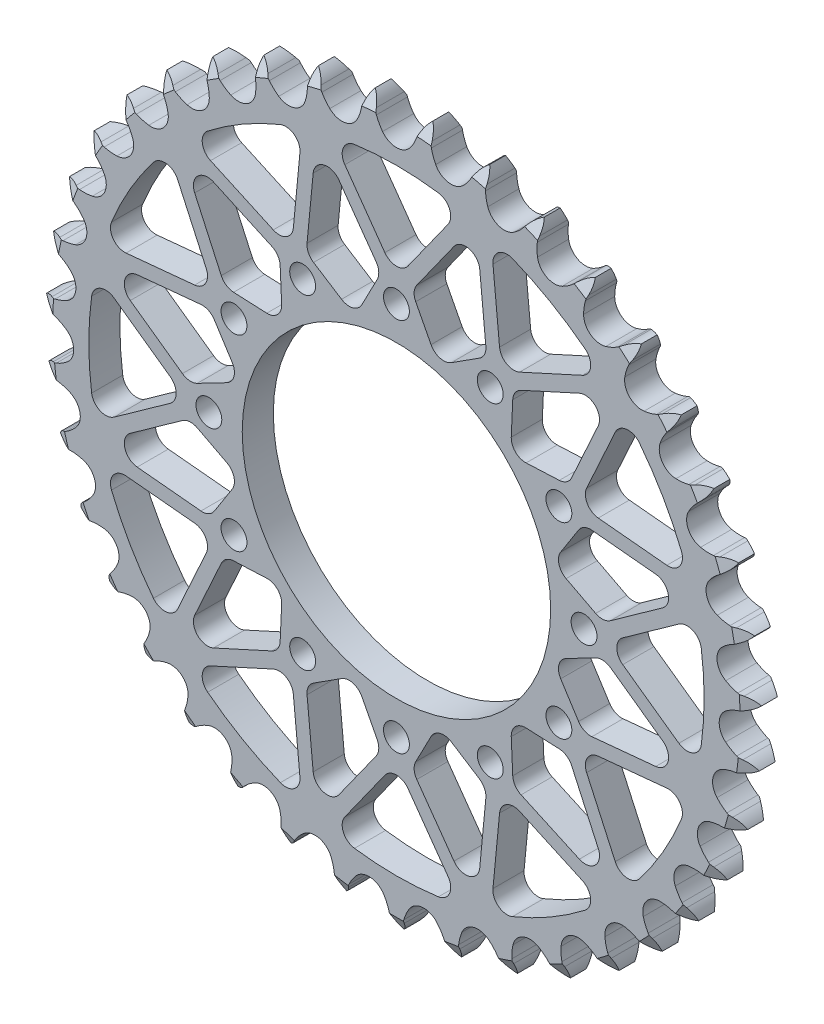
SolidWorks part; units mm, degrees
note: '?' marks a value the reader was unsure of.
material "7075-T6 (SN)"
ref_plane "Front Plane" through (0, 0, 0) normal (0, 0, 1) x (1, 0, 0)
ref_plane "Top Plane" through (0, 0, 0) normal (0, 1, 0) x (1, 0, 0)
ref_plane "Right Plane" through (0, 0, 0) normal (1, 0, 0) x (0, 0, -1)
sketch "Work Sketch" plane through (0, 0, 0) normal (0, 0, 1) x (1, 0, 0)
  line L0 (0, 0) -> (0, 160.4542) construction
  line L1 (-112.0919, 78.9148) -> (87.2579, 78.9148) construction
  line L2 (5.102, 120.8822) -> (5.102, 112.9699) construction
  line L3 (-12.8497, 82.6953) -> (16.7256, 82.6953) construction
  line L4 (5.102, 82.6953) -> (-6.0879, 74.4036) construction
  line L5 (5.102, 82.6953) -> (-4.6505, 79.1506) construction
  line L6 (-4.6505, 79.1506) -> (-6.8863, 85.3019)
  line L7 (-11.5114, 78.0206) -> (-7.1525, 78.0206) construction
  line L8 (-11.0765, 124.7602) -> (-11.0765, 110.2345) construction
  line L9 (0, 0) -> (-3.4402, 42.6146) construction
  circle A0 centre (0, 0) radius 78.9148
  circle A1 centre (0, 78.9148) radius 4.0088
  arc A2 (-4.6505, 79.1506) -> (-3.2209, 76.5281) centre (5.0804, 82.7541) ccw
  circle A3 centre (-11.0765, 78.0206) radius 6.4254
  point P23 (-3.2209, 76.5281)
  dimension "D1" = 157.8295
  dimension "D8" = 10.3767
  dimension "D2" = 8.0177
  dimension "D3" = 5.102
  dimension "D4" = 3.7806
  dimension "D5" = 36.538
  dimension "D6" = 16.564
  dimension "D7" = 10.3767
  dimension "D9" = 0.8942
  dimension "D10" = 11.0765
  dimension "D11" = 4.615
sketch "Teeth Sketch" plane through (0, 0, 0) normal (0, 0, 1) x (1, 0, 0)
  line L0 (5.0376, 80.2155) -> (4.6505, 79.1506)
  line L1 (-7.4865, 92.7372) -> (-4.7839, 59.2593) construction
  line L2 (0, 0) -> (-10.9133, 132.3061) construction
  line L3 (7.8951, 79.9848) -> (8.1063, 78.8717)
  line L4 (16093.3137, -199351.4616) -> (-16096.7539, 199394.0762) construction
  line L5 (0, 146.3285) -> (0, 56.9858) construction
  line L6 (17.8398, 78.3686) -> (17.287, 77.3797)
  line L7 (0, -200000) -> (0, 200160.4542) construction
  line L8 (20.6234, 77.6826) -> (20.6533, 76.5499)
  line L9 (-4.6505, 79.1506) -> (-6.8863, 85.3019) construction
  line L10 (44.1616, 67.154) -> (43.8313, 66.0702)
  line L11 (-5.0376, 80.2155) -> (-4.6505, 79.1506)
  line L12 (30.18, 74.4921) -> (29.4757, 73.6046)
  line L13 (32.8175, 73.3684) -> (32.6653, 72.2456)
  line L14 (41.7385, 68.6862) -> (40.901, 67.9232)
  line L15 (52.2161, 61.1014) -> (51.267, 60.4826)
  line L16 (54.362, 59.2003) -> (53.8621, 58.1836)
  line L17 (61.3413, 51.9341) -> (60.3052, 51.4756)
  line L18 (63.1544, 49.7134) -> (62.4979, 48.79)
  line L19 (68.8777, 41.4218) -> (67.7815, 41.1354)
  line L20 (70.3112, 38.939) -> (69.515, 38.1328)
  line L21 (74.6303, 29.8366) -> (73.5023, 29.7298)
  line L22 (75.6469, 27.156) -> (74.7318, 26.488)
  line L23 (78.45, 17.4787) -> (77.3195, 17.5542)
  line L24 (79.0234, 14.6698) -> (78.013, 14.1572)
  line L25 (80.2378, 4.6681) -> (79.1341, 4.9239)
  line L26 (80.3533, 1.8035) -> (79.2737, 1.4597)
  line L27 (79.9476, -8.2634) -> (78.8992, -7.8338)
  line L28 (79.602, -11.1094) -> (78.4813, -11.2756)
  line L29 (77.5867, -20.9809) -> (76.6208, -20.3887)
  line L30 (76.7891, -23.7346) -> (75.6562, -23.7189)
  line L31 (73.2164, -33.155) -> (72.358, -32.4155)
  line L32 (71.9874, -35.7451) -> (70.8717, -35.5478)
  line L33 (66.9499, -44.4704) -> (66.2212, -43.6028)
  line L34 (65.3213, -46.8298) -> (64.2517, -46.4561)
  line L35 (58.9493, -54.634) -> (58.3693, -53.6608)
  line L36 (56.9634, -56.7016) -> (55.9676, -56.1612)
  line L37 (49.422, -63.3827) -> (49.0056, -62.329)
  line L38 (47.1301, -65.1049) -> (46.2339, -64.4118)
  line L39 (38.6147, -70.4897) -> (38.3727, -69.3829)
  line L40 (36.0763, -71.822) -> (35.3028, -70.9941)
  line L41 (26.8073, -75.7712) -> (26.746, -74.6398)
  line L42 (24.088, -76.679) -> (23.4574, -75.7377)
  line L43 (14.3056, -79.0901) -> (14.4266, -77.9636)
  line L44 (11.4759, -79.55) -> (11.0044, -78.5198)
  line L45 (1.4334, -80.3607) -> (1.7335, -79.2682)
  line L46 (-1.4334, -80.3607) -> (-1.7335, -79.2682)
  line L47 (-11.4759, -79.55) -> (-11.0044, -78.5198)
  line L48 (-14.3056, -79.0901) -> (-14.4266, -77.9636)
  line L49 (-24.088, -76.679) -> (-23.4574, -75.7377)
  line L50 (-26.8073, -75.7712) -> (-26.746, -74.6398)
  line L51 (-36.0763, -71.822) -> (-35.3028, -70.9941)
  line L52 (-38.6147, -70.4897) -> (-38.3727, -69.3829)
  line L53 (-47.1301, -65.1049) -> (-46.2339, -64.4118)
  line L54 (-49.422, -63.3827) -> (-49.0056, -62.329)
  line L55 (-56.9634, -56.7016) -> (-55.9676, -56.1612)
  line L56 (-58.9493, -54.634) -> (-58.3693, -53.6608)
  line L57 (-65.3213, -46.8298) -> (-64.2517, -46.4561)
  line L58 (-66.9499, -44.4704) -> (-66.2212, -43.6028)
  line L59 (-71.9874, -35.7451) -> (-70.8717, -35.5478)
  line L60 (-73.2164, -33.155) -> (-72.358, -32.4155)
  line L61 (-76.7891, -23.7346) -> (-75.6562, -23.7189)
  line L62 (-77.5867, -20.9809) -> (-76.6208, -20.3887)
  line L63 (-79.602, -11.1094) -> (-78.4813, -11.2756)
  line L64 (-79.9476, -8.2634) -> (-78.8992, -7.8338)
  line L65 (-80.3533, 1.8035) -> (-79.2737, 1.4597)
  line L66 (-80.2378, 4.6681) -> (-79.1341, 4.9239)
  line L67 (-79.0234, 14.6698) -> (-78.013, 14.1572)
  line L68 (-78.45, 17.4787) -> (-77.3195, 17.5542)
  line L69 (-75.6469, 27.156) -> (-74.7318, 26.488)
  line L70 (-74.6303, 29.8366) -> (-73.5023, 29.7298)
  line L71 (-70.3112, 38.939) -> (-69.515, 38.1328)
  line L72 (-68.8777, 41.4218) -> (-67.7815, 41.1354)
  line L73 (-63.1544, 49.7134) -> (-62.4979, 48.79)
  line L74 (-61.3413, 51.9341) -> (-60.3052, 51.4756)
  line L75 (-54.362, 59.2003) -> (-53.8621, 58.1836)
  line L76 (-52.2161, 61.1014) -> (-51.267, 60.4826)
  line L77 (-44.1616, 67.154) -> (-43.8313, 66.0702)
  line L78 (-41.7385, 68.6862) -> (-40.901, 67.9232)
  line L79 (-32.8175, 73.3684) -> (-32.6653, 72.2456)
  line L80 (-30.18, 74.4921) -> (-29.4757, 73.6046)
  line L81 (-20.6234, 77.6826) -> (-20.6533, 76.5499)
  line L82 (-17.8398, 78.3686) -> (-17.287, 77.3797)
  line L83 (-7.8951, 79.9848) -> (-8.1063, 78.8717)
  arc A0 (-6.8336, 82.8459) -> (-5.0376, 80.2155) centre (-11.0765, 78.0206) cw
  circle A1 centre (-11.0765, 78.0206) radius 6.4254 construction
  arc A2 (-3.2209, 76.5281) -> (-4.6505, 79.1506) centre (5.0804, 82.7541) cw
  arc A3 (-4.6505, 79.1506) -> (-3.2209, 76.5281) centre (5.0804, 82.7541) ccw construction
  circle A4 centre (0, 78.9148) radius 4.0088 construction
  arc A5 (-3.2209, 76.5281) -> (3.2209, 76.5281) centre (0, 78.9148) ccw
  arc A6 (3.2209, 76.5281) -> (4.6505, 79.1506) centre (-5.0804, 82.7541) ccw
  arc A7 (6.8336, 82.8459) -> (5.0376, 80.2155) centre (11.0765, 78.0206) ccw
  arc A8 (6.5443, 82.8692) -> (7.8951, 79.9848) centre (1.5824, 78.787) cw
  arc A9 (9.0967, 76.0537) -> (8.1063, 78.8717) centre (18.2893, 80.8676) cw
  arc A10 (9.0967, 76.0537) -> (15.4552, 75.0204) centre (12.6588, 77.8928) ccw
  arc A11 (15.4552, 75.0204) -> (17.287, 77.3797) centre (8.2601, 82.4975) ccw
  arc A12 (20.0345, 80.6769) -> (17.8398, 78.3686) centre (23.4484, 75.2334) ccw
  arc A13 (19.7528, 80.7463) -> (20.6234, 77.6826) centre (14.2002, 77.5129) cw
  arc A14 (21.1788, 73.6096) -> (20.6533, 76.5499) centre (31.0245, 76.8865) cw
  arc A15 (21.1788, 73.6096) -> (27.2892, 71.5697) centre (24.9898, 74.8535) ccw
  arc A16 (27.2892, 71.5697) -> (29.4757, 73.6046) centre (21.3867, 80.1041) ccw
  arc A17 (32.7165, 76.4184) -> (30.18, 74.4921) centre (35.2131, 70.4978) ccw
  arc A18 (32.4496, 76.5321) -> (32.8175, 73.3684) centre (26.4502, 74.2313) cw
  arc A19 (32.7124, 69.2591) -> (32.6653, 72.2456) centre (42.9562, 70.9142) cw
  arc A20 (32.7124, 69.2591) -> (38.4163, 66.2654) centre (36.6735, 69.8756) ccw
  arc A21 (38.4163, 66.2654) -> (40.901, 67.9232) centre (33.9593, 75.6361) ccw
  arc A22 (44.5512, 70.1807) -> (41.7385, 68.6862) centre (46.0657, 63.9363) ccw
  arc A23 (44.306, 70.3358) -> (44.1616, 67.154) centre (38.0153, 69.0271) cw
  arc A24 (43.3987, 63.1147) -> (43.8313, 66.0702) centre (53.7754, 63.1052) cw
  arc A25 (43.3987, 63.1147) -> (48.5486, 59.2448) centre (47.4074, 63.0878) ccw
  arc A26 (48.5486, 59.2448) -> (51.267, 60.4826) centre (45.6524, 69.2092) ccw
  arc A27 (55.2321, 62.1253) -> (52.2161, 61.1014) centre (55.7253, 55.7189) ccw
  arc A28 (55.0149, 62.3178) -> (54.362, 59.2003) centre (48.5957, 62.0351) cw
  arc A29 (52.961, 55.3358) -> (53.8621, 58.1836) centre (63.2018, 53.6618) cw
  arc A30 (52.961, 55.3358) -> (57.4234, 50.6899) centre (56.9135, 54.6662) ccw
  arc A31 (57.4234, 50.6899) -> (60.3052, 51.4756) centre (56.1632, 60.9898) ccw
  arc A32 (64.4824, 52.461) -> (61.3413, 51.9341) centre (63.9416, 46.0584) ccw
  arc A33 (64.2989, 52.6858) -> (63.1544, 49.7134) centre (57.9175, 53.4365) cw
  arc A34 (61.1517, 46.1237) -> (62.4979, 48.79) centre (70.9913, 42.8287) cw
  arc A35 (61.1517, 46.1237) -> (64.811, 40.8221) centre (64.9456, 44.8287) ccw
  arc A36 (64.811, 40.8221) -> (67.7815, 41.1354) centre (65.2193, 51.1908) ccw
  arc A37 (72.0627, 41.4379) -> (68.8777, 41.4218) centre (70.5018, 35.205) ccw
  arc A38 (71.9177, 41.6892) -> (70.3112, 38.939) centre (65.7393, 43.4539) cw
  arc A39 (67.7585, 35.717) -> (69.515, 38.1328) centre (76.9422, 30.8862) cw
  arc A40 (67.7585, 35.717) -> (70.5201, 29.8971) centre (71.2956, 33.8302) ccw
  arc A41 (70.5201, 29.8971) -> (73.5023, 29.7298) centre (72.5864, 40.0659) ccw
  arc A42 (77.7767, 29.3416) -> (74.6303, 29.8366) centre (75.2361, 23.4398) ccw
  arc A43 (77.6738, 29.6129) -> (75.6469, 27.156) centre (71.8585, 32.3458) cw
  arc A44 (72.6105, 24.3852) -> (74.7318, 26.488) centre (80.9003, 18.1439) cw
  arc A45 (72.6105, 24.3852) -> (74.4027, 18.1977) centre (75.7991, 21.9555) ccw
  arc A46 (74.4027, 18.1977) -> (77.3195, 17.5542) centre (78.0734, 27.9034) ccw
  arc A47 (81.4762, 16.4854) -> (78.45, 17.4787) centre (78.0218, 11.0675) ccw
  arc A48 (81.4182, 16.7697) -> (79.0234, 14.6698) centre (76.1166, 20.4) cw
  arc A49 (75.5818, 12.4219) -> (78.013, 14.1572) centre (82.7631, 4.9316) cw
  arc A50 (75.5818, 12.4219) -> (76.3583, 6.027) centre (78.3394, 9.5121) ccw
  arc A51 (76.3583, 6.027) -> (79.1341, 4.9239) centre (81.5384, 15.0182) ccw
  arc A52 (83.0656, 3.2022) -> (80.2378, 4.6681) centre (78.7868, -1.5914) ccw
  arc A53 (83.0539, 3.4922) -> (80.3533, 1.8035) centre (78.4033, 7.9259) cw
  arc A54 (76.5957, 0.1368) -> (79.2737, 1.4597) centre (82.4825, -8.4084) cw
  arc A55 (76.5957, 0.1368) -> (76.3363, -6.2998) centre (78.8508, -3.1776) ccw
  arc A56 (76.3363, -6.2998) -> (78.8992, -7.8338) centre (82.8916, 1.7441) ccw
  arc A57 (82.5035, -10.1639) -> (79.9476, -8.2634) centre (77.5113, -14.2091) ccw
  arc A58 (82.5385, -9.8758) -> (79.602, -11.1094) centre (78.6594, -4.7535) cw
  arc A59 (75.6257, -12.1517) -> (78.4813, -11.2756) centre (80.0655, -21.5307) cw
  arc A60 (75.6257, -12.1517) -> (74.3372, -18.4634) centre (77.3199, -15.785) ccw
  arc A61 (74.3372, -18.4634) -> (76.6208, -20.3887) centre (82.0979, -11.5753) ccw
  arc A62 (79.8047, -23.2668) -> (77.5867, -20.9809) centre (74.2283, -26.4587) ccw
  arc A63 (79.8855, -22.9881) -> (76.7891, -23.7346) centre (76.8783, -17.3098) cw
  arc A64 (72.6971, -24.1256) -> (75.6562, -23.7189) centre (75.5749, -34.0953) cw
  arc A65 (72.6971, -24.1256) -> (70.4128, -30.1488) centre (73.7866, -27.9836) ccw
  arc A66 (70.4128, -30.1488) -> (72.358, -32.4155) centre (79.178, -24.5948) ccw
  arc A67 (75.039, -35.7671) -> (73.2164, -33.155) centre (69.0227, -38.0232) ccw
  arc A68 (75.1634, -35.5049) -> (71.9874, -35.7451) centre (73.106, -29.4178) cw
  arc A69 (67.8857, -35.4746) -> (70.8717, -35.5478) centre (69.127, -45.7768) cw
  arc A70 (67.8857, -35.4746) -> (64.6648, -41.0534) centre (68.3422, -39.4574) ccw
  arc A71 (64.6648, -41.0534) -> (66.2212, -43.6028) centre (74.2074, -36.9773) ccw
  arc A72 (68.3299, -47.341) -> (66.9499, -44.4704) centre (62.0296, -48.6028) ccw
  arc A73 (68.4947, -47.1022) -> (65.3213, -46.8298) centre (67.4404, -40.7639) cw
  arc A74 (61.3161, -45.9049) -> (64.2517, -46.4561) centre (60.8887, -56.2728) cw
  arc A75 (61.3161, -45.9049) -> (57.2419, -50.8948) centre (61.1278, -49.9093) ccw
  arc A76 (57.2419, -50.8948) -> (58.3693, -53.6608) centre (67.3148, -48.4022) ccw
  arc A77 (59.851, -57.6888) -> (58.9493, -54.634) centre (53.4299, -57.9236) ccw
  arc A78 (60.052, -57.4796) -> (56.9634, -56.7016) centre (60.0281, -51.0542) cw
  arc A79 (53.1584, -55.1462) -> (55.9676, -56.1612) centre (51.0734, -65.3113) cw
  arc A80 (53.1584, -55.1462) -> (48.3366, -59.4179) centre (52.3302, -59.0685) ccw
  arc A81 (48.3366, -59.4179) -> (49.0056, -62.329) centre (58.6789, -58.5735) ccw
  arc A82 (49.822, -66.5425) -> (49.422, -63.3827) centre (43.4464, -65.7443) ccw
  arc A83 (50.054, -66.3682) -> (47.1301, -65.1049) centre (51.0611, -60.0222) cw
  arc A84 (43.6239, -62.9593) -> (46.2339, -64.4118) centre (39.9354, -72.6583) cw
  arc A85 (43.6239, -62.9593) -> (38.1793, -66.4022) centre (42.1772, -66.698) ccw
  arc A86 (38.1793, -66.4022) -> (38.3727, -69.3829) centre (48.5231, -67.2277) ccw
  arc A87 (38.5026, -73.6728) -> (38.6147, -70.4897) centre (32.3376, -71.8622) ccw
  arc A88 (38.7596, -73.538) -> (36.0763, -71.822) centre (40.7716, -67.4357) cw
  arc A89 (32.9596, -69.1417) -> (35.3028, -70.9941) centre (27.763, -78.1234) cw
  arc A90 (32.9596, -69.1417) -> (27.0333, -71.6667) centre (30.932, -72.6) ccw
  arc A91 (27.0333, -71.6667) -> (26.746, -74.6398) centre (37.1107, -74.1408) ccw
  arc A92 (26.1861, -78.8951) -> (26.8073, -75.7712) centre (20.3913, -76.1189) ccw
  arc A93 (26.4613, -78.8032) -> (24.088, -76.679) centre (29.4261, -73.1027) cw
  arc A94 (21.4417, -73.5335) -> (23.4574, -75.7377) centre (14.8716, -81.5653) cw
  arc A95 (21.4417, -73.5335) -> (15.187, -75.0751) centre (18.8855, -76.6216) ccw
  arc A96 (15.187, -75.0751) -> (14.4266, -77.9636) centre (24.7371, -79.1336) ccw
  arc A97 (13.1913, -82.0739) -> (14.3056, -79.0901) centre (7.9169, -78.4042) ccw
  arc A98 (13.4777, -82.0274) -> (11.4759, -79.55) centre (17.3186, -76.8763) cw
  arc A99 (9.3684, -76.0207) -> (11.0044, -78.5198) centre (1.595, -82.8946) cw
  arc A100 (9.3684, -76.0207) -> (2.9475, -76.5391) centre (6.35, -78.6589) ccw
  arc A101 (2.9475, -76.5391) -> (1.7335, -79.2682) centre (11.7228, -82.077) ccw
  arc A102 (-0.1451, -83.1271) -> (1.4334, -80.3607) centre (-4.7625, -78.6589) ccw
  arc A103 (0.1451, -83.1271) -> (-1.4334, -80.3607) centre (4.7625, -78.6589) cw
  arc A104 (-2.9475, -76.5391) -> (-1.7335, -79.2682) centre (-11.7228, -82.077) cw
  arc A105 (-2.9475, -76.5391) -> (-9.3684, -76.0207) centre (-6.35, -78.6589) ccw
  arc A106 (-9.3684, -76.0207) -> (-11.0044, -78.5198) centre (-1.595, -82.8946) ccw
  arc A107 (-13.4777, -82.0274) -> (-11.4759, -79.55) centre (-17.3186, -76.8763) ccw
  arc A108 (-13.1913, -82.0739) -> (-14.3056, -79.0901) centre (-7.9169, -78.4042) cw
  arc A109 (-15.187, -75.0751) -> (-14.4266, -77.9636) centre (-24.7371, -79.1336) cw
  arc A110 (-15.187, -75.0751) -> (-21.4417, -73.5335) centre (-18.8855, -76.6216) ccw
  arc A111 (-21.4417, -73.5335) -> (-23.4574, -75.7377) centre (-14.8716, -81.5653) ccw
  arc A112 (-26.4613, -78.8032) -> (-24.088, -76.679) centre (-29.4261, -73.1027) ccw
  arc A113 (-26.1861, -78.8951) -> (-26.8073, -75.7712) centre (-20.3913, -76.1189) cw
  arc A114 (-27.0333, -71.6667) -> (-26.746, -74.6398) centre (-37.1107, -74.1408) cw
  arc A115 (-27.0333, -71.6667) -> (-32.9596, -69.1417) centre (-30.932, -72.6) ccw
  arc A116 (-32.9596, -69.1417) -> (-35.3028, -70.9941) centre (-27.763, -78.1234) ccw
  arc A117 (-38.7596, -73.538) -> (-36.0763, -71.822) centre (-40.7716, -67.4357) ccw
  arc A118 (-38.5026, -73.6728) -> (-38.6147, -70.4897) centre (-32.3376, -71.8622) cw
  arc A119 (-38.1793, -66.4022) -> (-38.3727, -69.3829) centre (-48.5231, -67.2277) cw
  arc A120 (-38.1793, -66.4022) -> (-43.6239, -62.9593) centre (-42.1772, -66.698) ccw
  arc A121 (-43.6239, -62.9593) -> (-46.2339, -64.4118) centre (-39.9354, -72.6583) ccw
  arc A122 (-50.054, -66.3682) -> (-47.1301, -65.1049) centre (-51.0611, -60.0222) ccw
  arc A123 (-49.822, -66.5425) -> (-49.422, -63.3827) centre (-43.4464, -65.7443) cw
  arc A124 (-48.3366, -59.4179) -> (-49.0056, -62.329) centre (-58.6789, -58.5735) cw
  arc A125 (-48.3366, -59.4179) -> (-53.1584, -55.1462) centre (-52.3302, -59.0685) ccw
  arc A126 (-53.1584, -55.1462) -> (-55.9676, -56.1612) centre (-51.0734, -65.3113) ccw
  arc A127 (-60.052, -57.4796) -> (-56.9634, -56.7016) centre (-60.0281, -51.0542) ccw
  arc A128 (-59.851, -57.6888) -> (-58.9493, -54.634) centre (-53.4299, -57.9236) cw
  arc A129 (-57.2419, -50.8948) -> (-58.3693, -53.6608) centre (-67.3148, -48.4022) cw
  arc A130 (-57.2419, -50.8948) -> (-61.3161, -45.9049) centre (-61.1278, -49.9093) ccw
  arc A131 (-61.3161, -45.9049) -> (-64.2517, -46.4561) centre (-60.8887, -56.2728) ccw
  arc A132 (-68.4947, -47.1022) -> (-65.3213, -46.8298) centre (-67.4404, -40.7639) ccw
  arc A133 (-68.3299, -47.341) -> (-66.9499, -44.4704) centre (-62.0296, -48.6028) cw
  arc A134 (-64.6648, -41.0534) -> (-66.2212, -43.6028) centre (-74.2074, -36.9773) cw
  arc A135 (-64.6648, -41.0534) -> (-67.8857, -35.4746) centre (-68.3422, -39.4574) ccw
  arc A136 (-67.8857, -35.4746) -> (-70.8717, -35.5478) centre (-69.127, -45.7768) ccw
  arc A137 (-75.1634, -35.5049) -> (-71.9874, -35.7451) centre (-73.106, -29.4178) ccw
  arc A138 (-75.039, -35.7671) -> (-73.2164, -33.155) centre (-69.0227, -38.0232) cw
  arc A139 (-70.4128, -30.1488) -> (-72.358, -32.4155) centre (-79.178, -24.5948) cw
  arc A140 (-70.4128, -30.1488) -> (-72.6971, -24.1256) centre (-73.7866, -27.9836) ccw
  arc A141 (-72.6971, -24.1256) -> (-75.6562, -23.7189) centre (-75.5749, -34.0953) ccw
  arc A142 (-79.8855, -22.9881) -> (-76.7891, -23.7346) centre (-76.8783, -17.3098) ccw
  arc A143 (-79.8047, -23.2668) -> (-77.5867, -20.9809) centre (-74.2283, -26.4587) cw
  arc A144 (-74.3372, -18.4634) -> (-76.6208, -20.3887) centre (-82.0979, -11.5753) cw
  arc A145 (-74.3372, -18.4634) -> (-75.6257, -12.1517) centre (-77.3199, -15.785) ccw
  arc A146 (-75.6257, -12.1517) -> (-78.4813, -11.2756) centre (-80.0655, -21.5307) ccw
  arc A147 (-82.5385, -9.8758) -> (-79.602, -11.1094) centre (-78.6594, -4.7535) ccw
  arc A148 (-82.5035, -10.1639) -> (-79.9476, -8.2634) centre (-77.5113, -14.2091) cw
  arc A149 (-76.3363, -6.2998) -> (-78.8992, -7.8338) centre (-82.8916, 1.7441) cw
  arc A150 (-76.3363, -6.2998) -> (-76.5957, 0.1368) centre (-78.8508, -3.1776) ccw
  arc A151 (-76.5957, 0.1368) -> (-79.2737, 1.4597) centre (-82.4825, -8.4084) ccw
  arc A152 (-83.0539, 3.4922) -> (-80.3533, 1.8035) centre (-78.4033, 7.9259) ccw
  arc A153 (-83.0656, 3.2022) -> (-80.2378, 4.6681) centre (-78.7868, -1.5914) cw
  arc A154 (-76.3583, 6.027) -> (-79.1341, 4.9239) centre (-81.5384, 15.0182) cw
  arc A155 (-76.3583, 6.027) -> (-75.5818, 12.4219) centre (-78.3394, 9.5121) ccw
  arc A156 (-75.5818, 12.4219) -> (-78.013, 14.1572) centre (-82.7631, 4.9316) ccw
  arc A157 (-81.4182, 16.7697) -> (-79.0234, 14.6698) centre (-76.1166, 20.4) ccw
  arc A158 (-81.4762, 16.4854) -> (-78.45, 17.4787) centre (-78.0218, 11.0675) cw
  arc A159 (-74.4027, 18.1977) -> (-77.3195, 17.5542) centre (-78.0734, 27.9034) cw
  arc A160 (-74.4027, 18.1977) -> (-72.6105, 24.3852) centre (-75.7991, 21.9555) ccw
  arc A161 (-72.6105, 24.3852) -> (-74.7318, 26.488) centre (-80.9003, 18.1439) ccw
  arc A162 (-77.6738, 29.6129) -> (-75.6469, 27.156) centre (-71.8585, 32.3458) ccw
  arc A163 (-77.7767, 29.3416) -> (-74.6303, 29.8366) centre (-75.2361, 23.4398) cw
  arc A164 (-70.5201, 29.8971) -> (-73.5023, 29.7298) centre (-72.5864, 40.0659) cw
  arc A165 (-70.5201, 29.8971) -> (-67.7585, 35.717) centre (-71.2956, 33.8302) ccw
  arc A166 (-67.7585, 35.717) -> (-69.515, 38.1328) centre (-76.9422, 30.8862) ccw
  arc A167 (-71.9177, 41.6892) -> (-70.3112, 38.939) centre (-65.7393, 43.4539) ccw
  arc A168 (-72.0627, 41.4379) -> (-68.8777, 41.4218) centre (-70.5018, 35.205) cw
  arc A169 (-64.811, 40.8221) -> (-67.7815, 41.1354) centre (-65.2193, 51.1908) cw
  arc A170 (-64.811, 40.8221) -> (-61.1517, 46.1237) centre (-64.9456, 44.8287) ccw
  arc A171 (-61.1517, 46.1237) -> (-62.4979, 48.79) centre (-70.9913, 42.8287) ccw
  arc A172 (-64.2989, 52.6858) -> (-63.1544, 49.7134) centre (-57.9175, 53.4365) ccw
  arc A173 (-64.4824, 52.461) -> (-61.3413, 51.9341) centre (-63.9416, 46.0584) cw
  arc A174 (-57.4234, 50.6899) -> (-60.3052, 51.4756) centre (-56.1632, 60.9898) cw
  arc A175 (-57.4234, 50.6899) -> (-52.961, 55.3358) centre (-56.9135, 54.6662) ccw
  arc A176 (-52.961, 55.3358) -> (-53.8621, 58.1836) centre (-63.2018, 53.6618) ccw
  arc A177 (-55.0149, 62.3178) -> (-54.362, 59.2003) centre (-48.5957, 62.0351) ccw
  arc A178 (-55.2321, 62.1253) -> (-52.2161, 61.1014) centre (-55.7253, 55.7189) cw
  arc A179 (-48.5486, 59.2448) -> (-51.267, 60.4826) centre (-45.6524, 69.2092) cw
  arc A180 (-48.5486, 59.2448) -> (-43.3987, 63.1147) centre (-47.4074, 63.0878) ccw
  arc A181 (-43.3987, 63.1147) -> (-43.8313, 66.0702) centre (-53.7754, 63.1052) ccw
  arc A182 (-44.306, 70.3358) -> (-44.1616, 67.154) centre (-38.0153, 69.0271) ccw
  arc A183 (-44.5512, 70.1807) -> (-41.7385, 68.6862) centre (-46.0657, 63.9363) cw
  arc A184 (-38.4163, 66.2654) -> (-40.901, 67.9232) centre (-33.9593, 75.6361) cw
  arc A185 (-38.4163, 66.2654) -> (-32.7124, 69.2591) centre (-36.6735, 69.8756) ccw
  arc A186 (-32.7124, 69.2591) -> (-32.6653, 72.2456) centre (-42.9562, 70.9142) ccw
  arc A187 (-32.4496, 76.5321) -> (-32.8175, 73.3684) centre (-26.4502, 74.2313) ccw
  arc A188 (-32.7165, 76.4184) -> (-30.18, 74.4921) centre (-35.2131, 70.4978) cw
  arc A189 (-27.2892, 71.5697) -> (-29.4757, 73.6046) centre (-21.3867, 80.1041) cw
  arc A190 (-27.2892, 71.5697) -> (-21.1788, 73.6096) centre (-24.9898, 74.8535) ccw
  arc A191 (-21.1788, 73.6096) -> (-20.6533, 76.5499) centre (-31.0245, 76.8865) ccw
  arc A192 (-19.7528, 80.7463) -> (-20.6234, 77.6826) centre (-14.2002, 77.5129) ccw
  arc A193 (-20.0345, 80.6769) -> (-17.8398, 78.3686) centre (-23.4484, 75.2334) cw
  arc A194 (-15.4552, 75.0204) -> (-17.287, 77.3797) centre (-8.2601, 82.4975) cw
  arc A195 (-15.4552, 75.0204) -> (-9.0967, 76.0537) centre (-12.6588, 77.8928) ccw
  arc A196 (-9.0967, 76.0537) -> (-8.1063, 78.8717) centre (-18.2893, 80.8676) ccw
  arc A197 (-6.5443, 82.8692) -> (-7.8951, 79.9848) centre (-1.5824, 78.787) ccw
  point P77 (0, 0)
  dimension "D1" = 4.615
  dimension "D2" = 4.715
  dimension "D3" = 39
extrude "Extrusion" add sketch "Teeth Sketch" along normal blind 7.2136
sketch "Sketch1" plane through (0, 0, 0) normal (0, 0, -1) x (-1, 0, 0)
  circle A0 centre (0, 0) radius 78.9443
  circle A1 centre (0, 0) radius 35.7643
  dimension "D1" = 43.18
extrude "Cut-Extrude" cut sketch "Sketch1" against normal through all both and the other way through all contours A1
ref_axis "Axis1" [suppressed] through (0, 0, 7.2136) along (0, 0, -1)?
ref_plane "Sprocket Center Plane" through (0, 0, 3.6068) normal (0, 0, 1) x (1, 0, 0)
sketch "Pitch Circle" plane through (0, 0, 3.6068) normal (0, 0, -1) x (-1, 0, 0)
  circle A0 centre (0, 0) radius 82.9531 construction
  dimension "D1" = 165.9063
sketch "Chain Pitch Circle" plane through (0, 0, 0) normal (0, 0, -1) x (-1, 0, 0)
  circle A0 centre (0, 0) radius 82.9531 construction
  dimension "D1" = 165.9063
ref_plane "Center Plane" through (0, 0, 3.6068) normal (0, 0, 1) x (1, 0, 0)
hole_wizard "Ø6.0mm Dowel Hole1" positions "Sketch7" profile "Sketch8" hole size "Ø6.0" standard "ANSI Metric" end condition through all
sketch "Sketch7" plane through (0, 0, 7.2136) normal (0, 0, 1) x (1, 0, 0)
  point P0 (-43.5, 0)
  dimension "D1" = 43.5
sketch "Sketch8" plane through (-43.5, 0, 7.2136) normal (1, 0, 0) x (0, -1, 0)
  line L0 (0, 0) -> (0, 7.2136)
  line L1 (0, 7.2136) -> (3, 7.2136)
  line L2 (3, 7.2136) -> (3, 0)
  line L5 (3, 0) -> (0, 0)
  line L11 (0, -6.35) -> (0, 107.95) construction
  dimension "Thru Hole Dia." = 6
  dimension "Thru Hole Depth" = 7.2136
pattern_circular "CirPattern1" count 12 over 360 about axis through (0, 0, 0) along (0, 0, 1) of "Ø6.0mm Dowel Hole1"
ref_plane "Plane1" through (0, 0, 3.6068) normal (0, 0, -1) x (-1, 0, 0)
sketch "Sketch9" plane through (0, 0, 0) normal (0, 0, 1) x (1, 0, 0)
  line L0 (-43.5, 0) -> (-71.3499, 0) construction
  line L1 (-69.7539, 15.0068) -> (-48.707, 0)
  line L2 (-69.7539, -15.0068) -> (-48.707, 0)
  line L11 (-43.5, 0) -> (-37.6721, 21.75) construction
  line L13 (-68.9187, 18.4667) -> (-36.1404, 9.6838) construction
  line L18 (-43.3252, 20.9264) -> (-36.1404, 9.6838)
  line L19 (-47.9839, 3.5399) -> (-36.1404, 9.6838)
  line L20 (-43.3252, 20.9264) -> (-68.9187, 18.4667)
  line L21 (-47.9839, 3.5399) -> (-68.9187, 18.4667)
  circle A0 centre (0, 0) radius 74.9059 construction
  arc A1 (-57.4234, 50.6899) -> (-52.961, 55.3358) centre (-56.9135, 54.6662) ccw construction
  circle A2 centre (-43.5, 0) radius 3 construction
  circle A3 centre (-43.5, 0) radius 5.207
  circle A4 centre (-37.6721, 21.75) radius 3 construction
  circle A6 centre (-37.6721, 21.75) radius 5.207
  circle A196 centre (0, 0) radius 71.3499
  circle A197 centre (0, 0) radius 35.7643 construction
  circle A198 centre (0, 0) radius 35.7643
  circle A199 centre (0, 0) radius 37.4153 construction
  point P17 (-40.5861, 10.875)
  dimension "D1" = 3.556
  dimension "D2" = 1.651
  dimension "D3" = 10.414
  dimension "D4" = 3.302
extrude "Cut-Extrude2" cut sketch "Sketch9" along normal through all contours L1 A196 L2 | L21 L19 L18 L20
fillet "Fillet2" radius 3.302 7 edges at (-68.9187, 18.4667, 3.6068) (-36.1404, 9.6838, 3.6068) (-47.9839, 3.5399, 3.6068) (-43.3252, 20.9264, 3.6068) (-69.7539, -15.0068, 3.6068) (-48.707, 0, 3.6068) (-69.7539, 15.0068, 3.6068)
pattern_circular "CirPattern3" count 12 over 360 about axis through (0, 0, 0) along (0, 0, 1) of "Cut-Extrude2", "Fillet2"
sketch "Sketch14" plane through (0, 0, 7.2136) normal (0, 0, 1) x (1, 0, 0)
  line L0 (-46.191, -4.47) -> (-39.3483, -8.0197) construction
  line L1 (-38.1786, 5.765) -> (-38.5782, 5.5577)
  line L2 (-43.5, 0) -> (-38.293, 0) construction
  line L3 (-38.1786, -5.765) -> (-38.5782, -5.5577)
  line L4 (-30.1812, 24.082) -> (-30.6308, 24.1022)
  line L5 (-35.9462, 14.0967) -> (-36.1886, 14.4759)
  line L6 (-14.0967, 35.9462) -> (-14.4759, 36.1886)
  line L7 (-24.082, 30.1812) -> (-24.1022, 30.6308)
  line L8 (5.765, 38.1786) -> (5.5577, 38.5782)
  line L9 (-5.765, 38.1786) -> (-5.5577, 38.5782)
  line L10 (24.082, 30.1812) -> (24.1022, 30.6308)
  line L11 (14.0967, 35.9462) -> (14.4759, 36.1886)
  line L12 (35.9462, 14.0967) -> (36.1886, 14.4759)
  line L13 (30.1812, 24.082) -> (30.6308, 24.1022)
  line L14 (38.1786, -5.765) -> (38.5782, -5.5577)
  line L15 (38.1786, 5.765) -> (38.5782, 5.5577)
  line L16 (30.1812, -24.082) -> (30.6308, -24.1022)
  line L17 (35.9462, -14.0967) -> (36.1886, -14.4759)
  line L18 (14.0967, -35.9462) -> (14.4759, -36.1886)
  line L19 (24.082, -30.1812) -> (24.1022, -30.6308)
  line L20 (-5.765, -38.1786) -> (-5.5577, -38.5782)
  line L21 (5.765, -38.1786) -> (5.5577, -38.5782)
  line L22 (-24.082, -30.1812) -> (-24.1022, -30.6308)
  line L23 (-14.0967, -35.9462) -> (-14.4759, -36.1886)
  line L24 (-35.9462, -14.0967) -> (-36.1886, -14.4759)
  line L25 (-30.1812, -24.082) -> (-30.6308, -24.1022)
  arc A0 (-39.2207, -2.9665) -> (-39.2207, 2.9665) centre (-43.5, 0) ccw
  circle A1 centre (0, 0) radius 35.7643 construction
  arc A2 (-38.5782, -5.5577) -> (-39.2207, -2.9665) centre (-37.7594, -3.9795) cw
  arc A3 (-38.1786, 5.765) -> (-35.9462, 14.0967) centre (-40.8688, 10.9508) ccw
  arc A4 (-38.1786, 5.765) -> (-35.9462, 14.0967) centre (-40.8688, 10.9508) ccw
  arc A5 (-38.5782, 5.5577) -> (-39.2207, 2.9665) centre (-37.7594, 3.9795) ccw
  circle A6 centre (0, 0) radius 35.7643
  arc A7 (-30.1812, 24.082) -> (-24.082, 30.1812) centre (-29.918, 29.918) ccw
  arc A8 (-30.6308, 24.1022) -> (-32.4828, 22.1794) centre (-30.7109, 22.326) ccw
  arc A9 (-35.4494, 17.0413) -> (-32.4828, 22.1794) centre (-37.6721, 21.75) ccw
  arc A10 (-36.1886, 14.4759) -> (-35.4494, 17.0413) centre (-34.6904, 15.4334) cw
  arc A11 (-14.0967, 35.9462) -> (-5.765, 38.1786) centre (-10.9508, 40.8688) ccw
  arc A12 (-14.4759, 36.1886) -> (-17.0413, 35.4494) centre (-15.4334, 34.6904) ccw
  arc A13 (-22.1794, 32.4828) -> (-17.0413, 35.4494) centre (-21.75, 37.6721) ccw
  arc A14 (-24.1022, 30.6308) -> (-22.1794, 32.4828) centre (-22.326, 30.7109) cw
  arc A15 (5.765, 38.1786) -> (14.0967, 35.9462) centre (10.9508, 40.8688) ccw
  arc A16 (5.5577, 38.5782) -> (2.9665, 39.2207) centre (3.9795, 37.7594) ccw
  arc A17 (-2.9665, 39.2207) -> (2.9665, 39.2207) centre (0, 43.5) ccw
  arc A18 (-5.5577, 38.5782) -> (-2.9665, 39.2207) centre (-3.9795, 37.7594) cw
  arc A19 (24.082, 30.1812) -> (30.1812, 24.082) centre (29.918, 29.918) ccw
  arc A20 (24.1022, 30.6308) -> (22.1794, 32.4828) centre (22.326, 30.7109) ccw
  arc A21 (17.0413, 35.4494) -> (22.1794, 32.4828) centre (21.75, 37.6721) ccw
  arc A22 (14.4759, 36.1886) -> (17.0413, 35.4494) centre (15.4334, 34.6904) cw
  arc A23 (35.9462, 14.0967) -> (38.1786, 5.765) centre (40.8688, 10.9508) ccw
  arc A24 (36.1886, 14.4759) -> (35.4494, 17.0413) centre (34.6904, 15.4334) ccw
  arc A25 (32.4828, 22.1794) -> (35.4494, 17.0413) centre (37.6721, 21.75) ccw
  arc A26 (30.6308, 24.1022) -> (32.4828, 22.1794) centre (30.7109, 22.326) cw
  arc A27 (38.1786, -5.765) -> (35.9462, -14.0967) centre (40.8688, -10.9508) ccw
  arc A28 (38.5782, -5.5577) -> (39.2207, -2.9665) centre (37.7594, -3.9795) ccw
  arc A29 (39.2207, 2.9665) -> (39.2207, -2.9665) centre (43.5, 0) ccw
  arc A30 (38.5782, 5.5577) -> (39.2207, 2.9665) centre (37.7594, 3.9795) cw
  arc A31 (30.1812, -24.082) -> (24.082, -30.1812) centre (29.918, -29.918) ccw
  arc A32 (30.6308, -24.1022) -> (32.4828, -22.1794) centre (30.7109, -22.326) ccw
  arc A33 (35.4494, -17.0413) -> (32.4828, -22.1794) centre (37.6721, -21.75) ccw
  arc A34 (36.1886, -14.4759) -> (35.4494, -17.0413) centre (34.6904, -15.4334) cw
  arc A35 (14.0967, -35.9462) -> (5.765, -38.1786) centre (10.9508, -40.8688) ccw
  arc A36 (14.4759, -36.1886) -> (17.0413, -35.4494) centre (15.4334, -34.6904) ccw
  arc A37 (22.1794, -32.4828) -> (17.0413, -35.4494) centre (21.75, -37.6721) ccw
  arc A38 (24.1022, -30.6308) -> (22.1794, -32.4828) centre (22.326, -30.7109) cw
  arc A39 (-5.765, -38.1786) -> (-14.0967, -35.9462) centre (-10.9508, -40.8688) ccw
  arc A40 (-5.5577, -38.5782) -> (-2.9665, -39.2207) centre (-3.9795, -37.7594) ccw
  arc A41 (2.9665, -39.2207) -> (-2.9665, -39.2207) centre (0, -43.5) ccw
  arc A42 (5.5577, -38.5782) -> (2.9665, -39.2207) centre (3.9795, -37.7594) cw
  arc A43 (-24.082, -30.1812) -> (-30.1812, -24.082) centre (-29.918, -29.918) ccw
  arc A44 (-24.1022, -30.6308) -> (-22.1794, -32.4828) centre (-22.326, -30.7109) ccw
  arc A45 (-17.0413, -35.4494) -> (-22.1794, -32.4828) centre (-21.75, -37.6721) ccw
  arc A46 (-14.4759, -36.1886) -> (-17.0413, -35.4494) centre (-15.4334, -34.6904) cw
  arc A47 (-35.9462, -14.0967) -> (-38.1786, -5.765) centre (-40.8688, -10.9508) ccw
  arc A48 (-36.1886, -14.4759) -> (-35.4494, -17.0413) centre (-34.6904, -15.4334) ccw
  arc A49 (-32.4828, -22.1794) -> (-35.4494, -17.0413) centre (-37.6721, -21.75) ccw
  arc A50 (-30.6308, -24.1022) -> (-32.4828, -22.1794) centre (-30.7109, -22.326) cw
  point P10 (-40.7583, -4.4268)
  point P16 (-40.7583, 4.4268)
  point P144 (0, 0)
  dimension "D2" = 1.778
  dimension "D1" = 2.54
  dimension "D3" = 12
extrude "Cut-Extrude7" [suppressed] cut sketch "Sketch14" against normal through all
sketch "Sketch15" plane through (0, 0, 0) normal (1, 0, 0) x (0, 0, -1)
  line L0 (-5.4356, -82.9722) -> (-7.2136, -79.6702)
  line L1 (-7.2136, -82.9722) -> (-5.4356, -82.9722)
  line L2 (-7.2136, -82.9722) -> (-7.2136, -79.6702)
  line L3 (-7.2136, -79.6702) -> (-5.4356, -79.6702)
  line L4 (-5.4356, -82.9722) -> (-5.4356, -79.6702)
  dimension "D1" = 1.778
  dimension "D2" = 3.302
revolve "Cut-Revolve1" cut sketch "Sketch15" angle 360 about axis through (0, 0, 7.2136) along (0, 0, -1)
ref_plane "Plane2" through (0, 0, 3.6068) normal (0, 0, -1) x (-1, 0, 0)
mirror "Mirror1" about plane through (0, 0, 3.6068) normal (0, 0, -1) of "Cut-Revolve1"
sketch "Sketch18" plane through (0, 0, 0) normal (0, 0, -1) x (-1, 0, 0)
  arc A0 (38.0864, 12.7289) -> (39.3483, 8.0197) centre (40.8688, 10.9508) ccw construction
  arc A1 (38.0864, 12.7289) -> (39.3483, 8.0197) centre (40.8688, 10.9508) ccw construction
  arc A2 (52.4777, 2.6886) -> (52.4777, -2.6886) centre (54.3947, 0) ccw construction
  arc A3 (52.4777, 2.6886) -> (52.4777, -2.6886) centre (54.3947, 0) ccw construction
  circle A4 centre (40.8688, 10.9508) radius 2.3812
  circle A5 centre (54.3947, 0) radius 2.3812
  circle A6 centre (0, 0) radius 82.9722
  circle A7 centre (40.8688, -10.9508) radius 2.3812
  circle A8 centre (47.1072, -27.1973) radius 2.3812
  circle A9 centre (29.918, -29.918) radius 2.3812
  circle A10 centre (27.1973, -47.1072) radius 2.3812
  circle A11 centre (10.9508, -40.8688) radius 2.3812
  circle A12 centre (0, -54.3947) radius 2.3812
  circle A13 centre (-10.9508, -40.8688) radius 2.3812
  circle A14 centre (-27.1973, -47.1072) radius 2.3813
  circle A15 centre (-29.918, -29.918) radius 2.3812
  circle A16 centre (-47.1072, -27.1973) radius 2.3812
  circle A17 centre (-40.8688, -10.9508) radius 2.3812
  circle A18 centre (-54.3947, 0) radius 2.3812
  circle A19 centre (-40.8688, 10.9508) radius 2.3812
  circle A20 centre (-47.1072, 27.1973) radius 2.3812
  circle A21 centre (-29.918, 29.918) radius 2.3812
  circle A22 centre (-27.1973, 47.1072) radius 2.3813
  circle A23 centre (-10.9508, 40.8688) radius 2.3812
  circle A24 centre (0, 54.3947) radius 2.3812
  circle A25 centre (10.9508, 40.8688) radius 2.3812
  circle A26 centre (27.1973, 47.1072) radius 2.3813
  circle A27 centre (29.918, 29.918) radius 2.3812
  circle A28 centre (47.1072, 27.1973) radius 2.3812
  point P58 (0, 0)
  dimension "D1" = 4.7625
  dimension "D2" = 12
equation "\"P\"= 0.500'//Chain Pitch"
equation "\"N\"= 39'//Number of Teeth"
equation "\"Dr\"= 5 / 16'//Roller Diameter"
equation "\"Ds\"= 1.0005 * \"Dr\" + 0.003'Seating Curve DIameter"
equation "\"R\"= \"Ds\" / 2"
equation "\"A\"= 35 + 60 / \"N\""
equation "\"B\"= 18 - 56 / \"N\""
equation "\"ac\"= 0.8 * \"Dr\""
equation "\"M\"= 0.8 * \"Dr\" * cos ( 35 + 60 / \"N\" )"
equation "\"T\"= 0.8 * \"Dr\" * sin ( 35 + 60 / \"N\" )"
equation "\"E\"= 1.3025 * \"Dr\" + 0.0015"
equation "\"Chordal Length of Arc xy\"= ( 2.605 * \"Dr\" + 0.003 ) * sin ( 9 - 28 / \"N\" )"
equation "\"yz\"= \"Dr\" * ( 1.4 * sin ( 17 - 64 / \"N\" ) - 0.8 * sin ( 18 - 56 / \"N\" ) )"
equation "\"ab\"= 1.4 * \"Dr\""
equation "\"W\"= 1.4 * \"Dr\" * cos ( 180 / \"N\" )"
equation "\"V\"= 1.4 * \"Dr\" * sin ( 180 / \"N\" )"
equation "\"F\"= \"Dr\" * ( 0.8 * cos ( 18 - 56 / \"N\" ) + 1.4 * cos ( 17 - 64 / \"N\" ) - 1.3025 )"
equation "\"H\"= sqr ( \"F\" ^ 2 - ( 1.4 * \"Dr\" - \"P\" / 2 ) ^ 2 )"
equation "\"S\"= \"P\" / 2 * cos ( 180 / \"N\" ) + \"H\" * sin ( 180 / \"N\" )"
equation "\"PD\"= \"P\" / ( sin ( 180 / \"N\" ) )"
equation "\"D1@Work Sketch\" = \"PD\""
equation "\"D3@Work Sketch\" = \"M\""
equation "\"D4@Work Sketch\" = \"T\""
equation "\"D5@Work Sketch\" = \"A\""
equation "\"D6@Work Sketch\" = \"B\""
equation "\"D7@Work Sketch\" = \"E\""
equation "\"D8@Work Sketch\" = \"E\""
equation "\"D9@Work Sketch\" = \"V\""
equation "\"D10@Work Sketch\" = \"W\""
equation "\"D2@Work Sketch\" = \"R\" * 2"
equation "\"D11@Work Sketch\" = 180 / \"N\""
equation "\"D2@Teeth Sketch\" = 180 / \"N\" + 0.1"
equation "\"D3@Teeth Sketch\" = \"N\""
equation "\"Edge Thickness\"=1.7"
equation "\"D1@Sketch1\"=\"Edge Thickness\""
equation "\"InnerRib\"=0.060000"
equation "\"ST\"= 0.284'//Sprocket Thickness"
